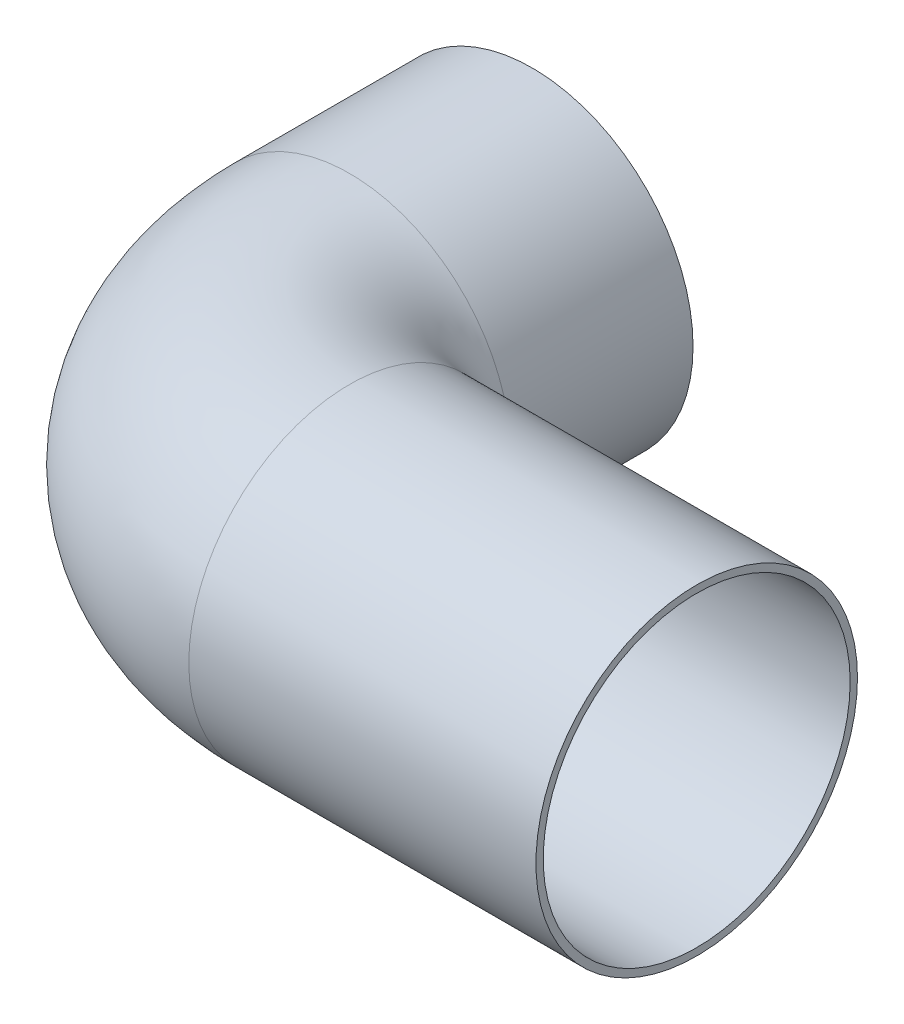
SolidWorks part; units mm, degrees
ref_plane "Front Plane" through (0, 0, 0) normal (0, 0, 1) x (1, 0, 0)
ref_plane "Top Plane" through (0, 0, 0) normal (0, 1, 0) x (1, 0, 0)
ref_plane "Right Plane" through (0, 0, 0) normal (1, 0, 0) x (0, 0, -1)
sketch "Sketch9" plane through (0, 0, 0) normal (0, 1, 0) x (1, 0, 0)
  line L5 (22.5, 47.5) -> (22.5, 72.5)
  line L6 (47.5, 22.5) -> (95, 22.5)
  arc A5 (22.5, 47.5) -> (47.5, 22.5) centre (47.5, 47.5) ccw
  point P4 (45, 45)
  point P6 (45, 45)
  point P7 (80, 45)
  point P8 (80, 45)
  point P9 (22.5, 22.5)
  dimension "D1" = 25
  dimension "D2" = 47.5
ref_plane "Plane5" through (95, 0, -22.5) normal (1, 0, 0) x (0, 0, -1)
sketch "Sketch11" plane through (95, 0, -22.5) normal (1, 0, 0) x (0, 0, -1)
  circle A0 centre (0, 0) radius 22
  circle A1 centre (0, 0) radius 21
  dimension "D1" = 42
  dimension "D2" = 44
sweep "Sweep10" add profiles "Sketch11" path "Sketch9"
